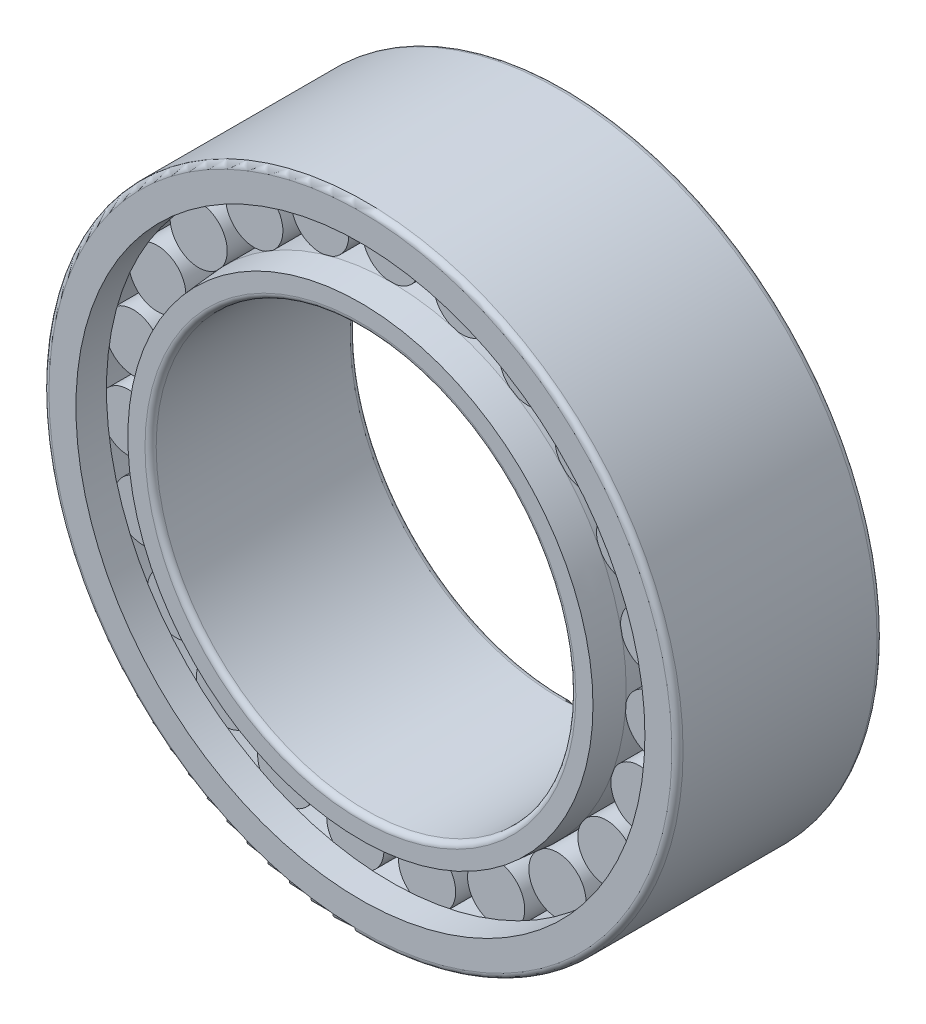
SolidWorks part; units mm, degrees
ref_plane "Front Plane" through (0, 0, 0) normal (0, 0, 1) x (1, 0, 0)
ref_plane "Top Plane" through (0, 0, 0) normal (0, 1, 0) x (1, 0, 0)
ref_plane "Right Plane" through (0, 0, 0) normal (1, 0, 0) x (0, 0, -1)
sketch "BaseSke" plane through (0, 0, 0) normal (1, 0, 0) x (0, 0, -1)
  line L0 (-47.2296, 0) -> (24.6132, 0) construction
  line L1 (-47.2296, 28.25) -> (24.6132, 28.25) construction
  line L2 (0, 129.5214) -> (0, -86.3012) construction
  line L3 (-7.7, 28.25) -> (-7.7, 31.3167) construction
  line L4 (-11, 34) -> (11, 34) construction
  line L5 (-11, 22.5) -> (11, 22.5) construction
  line L6 (-7.7, 25.1833) -> (7.7, 25.1833)
  line L7 (-7.7, 25.1833) -> (-7.7, 28.25)
  line L8 (-7.7, 28.25) -> (7.7, 28.25)
  line L9 (7.7, 25.1833) -> (7.7, 28.25)
  line L10 (-7.7, 31.3167) -> (7.7, 31.3167) construction
  line L11 (7.7, 31.3167) -> (7.7, 28.25) construction
  dimension "D2" = 15.4
  dimension "D1" = 56.5
  dimension "D3" = 3.0667
revolve "Roller" add sketch "BaseSke" angle 360 about L8
sketch "OuterRaceSke" plane through (0, 0, 0) normal (1, 0, 0) x (0, 0, -1)
  line L0 (0, 0) -> (0, 87.5396) construction
  line L1 (-11, 34) -> (11, 34)
  line L2 (-11, 34) -> (-11, 30.508)
  line L3 (-11, 30.508) -> (-7.725, 30.508)
  line L4 (11, 34) -> (11, 30.508)
  line L5 (-50.3916, 0) -> (55.2197, 0) construction
  line L6 (-7.7, 31.3167) -> (7.7, 31.3167) construction
  line L7 (7.725, 30.508) -> (11, 30.508)
  line L9 (-7.725, 30.508) -> (-7.725, 31.2747)
  line L10 (-7.725, 31.2747) -> (7.725, 31.2747)
  line L11 (7.725, 30.508) -> (7.725, 31.2747)
  dimension "D1" = 15.45
  dimension "D3" = 0.042
  dimension "D2" = 0.7667
revolve "OuterRace" add sketch "OuterRaceSke" angle 360 about L5
sketch "InnerRaceSke" plane through (0, 0, 0) normal (1, 0, 0) x (0, 0, -1)
  line L0 (-70.8626, 0) -> (113.5527, 0) construction
  line L1 (0, 58.441) -> (0, -70.8113) construction
  line L2 (-11, 22.5) -> (11, 22.5)
  line L3 (-11, 22.5) -> (-11, 25.992)
  line L4 (-7.725, 25.992) -> (-7.725, 25.2253)
  line L5 (-7.725, 25.992) -> (-11, 25.992)
  line L6 (0, 129.5214) -> (0, -86.3012) construction
  line L7 (-7.725, 25.2253) -> (7.725, 25.2253)
  line L9 (11, 22.5) -> (11, 25.992)
  line L10 (7.725, 25.992) -> (11, 25.992)
  line L11 (7.725, 25.2253) -> (7.725, 25.992)
  line L13 (-7.7, 25.1833) -> (7.7, 25.1833) construction
  point P17 (0, 22.5)
  dimension "D1" = 15.45
  dimension "D2" = 0.042
  dimension "D3" = 0.7667
revolve "InnerRace" add sketch "InnerRaceSke" angle 360 about L0
fillet "Fillet1" radius 0.6 4 edges at (22.5, 0, 11) (34, 0, -11) (34, 0, 11) (22.5, 0, -11)
sketch "NJSke" plane through (0, 0, 0) normal (1, 0, 0) x (0, 0, -1)
  line L0 (-35.6078, 0) -> (44.429, 0) construction
  line L1 (11, 25.992) -> (7.725, 25.992)
  line L2 (7.725, 25.992) -> (7.725, 25.2253)
  line L3 (7.725, 25.2253) -> (11, 24.9388)
  line L4 (11, 24.9388) -> (11, 25.992)
  dimension "D1" = 5
revolve "NJ" cut sketch "NJSke" angle 360 about L0
mirror "NU" about plane through (0, 0, 0) normal (0, 0, 1) of "NJ"
pattern_circular "CirPatternBall" count 23 over 360 about axis through (0, 0, 50.3916) along (0, 0, -1) of "Roller"
sketch "SimplifiedSke" plane through (0, 0, 0) normal (1, 0, 0) x (0, 0, -1)
  line L0 (37.5911, 0) -> (-37.5911, 0) construction
  line L1 (-13.1351, 28.25) -> (13.151, 28.25) construction
  line L2 (-7.7, 31.3167) -> (7.7, 31.3167)
  line L3 (-7.7, 31.3167) -> (-7.7, 25.1833)
  line L4 (-7.7, 25.1833) -> (7.7, 25.1833)
  line L5 (7.7, 31.3167) -> (7.7, 25.1833)
  line L6 (-47.2296, 28.25) -> (24.6132, 28.25) construction
revolve "Simplified" [suppressed] add sketch "SimplifiedSke" angle 360 about L0
equation "\"D2@BaseSke\" = \"Bearing_Thickness@BaseSke\"*0.7"
equation "\"D1@BaseSke\" =  ( \"Bearing_Inside_Diameter@BaseSke\" + \"Bearing_Outside_Diameter@BaseSke\" )  / 2"
equation "\"D3@BaseSke\" =  ( \"Bearing_Outside_Diameter@BaseSke\" - \"Bearing_Inside_Diameter@BaseSke\" )  / 7.5"
equation "\"D1@OuterRaceSke\" = \"Bearing_Thickness@BaseSke\"*0.7+0.05"
equation "\"D3@OuterRaceSke\" = 0.02+\"Bearing_Thickness@BaseSke\" * 0.001"
equation "\"D2@OuterRaceSke\" = \"D3@BaseSke\" * 0.25"
equation "\"D1@InnerRaceSke\" = \"Bearing_Thickness@BaseSke\"*0.7+0.05"
equation "\"D2@InnerRaceSke\" = \"D3@OuterRaceSke\""
equation "\"D3@InnerRaceSke\" = \"D2@OuterRaceSke\""
equation "\"D1@CirPatternBall\" =  int(  ( \"Bearing_Outside_Diameter@BaseSke\" + \"Bearing_Inside_Diameter@BaseSke\" )  / 2 *  pi  /  ( \"Bearing_Outside_Diameter@BaseSke\" - \"Bearing_Inside_Diameter@BaseSke\" ) * 3 ) "
